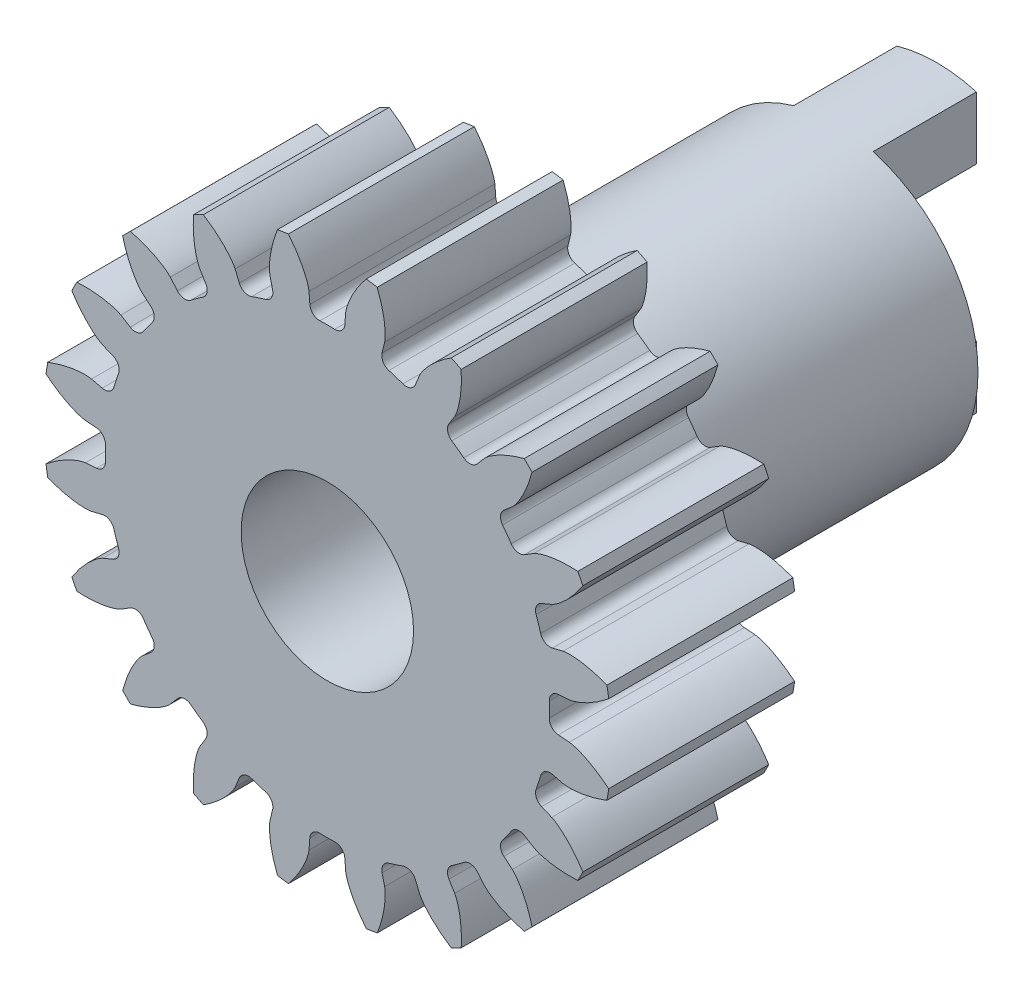
SolidWorks part; units mm, degrees
ref_plane "Front Plane" through (0, 0, 0) normal (0, 0, 1) x (1, 0, 0)
ref_plane "Top Plane" through (0, 0, 0) normal (0, 1, 0) x (1, 0, 0)
ref_plane "Right Plane" through (0, 0, 0) normal (1, 0, 0) x (0, 0, -1)
ref_axis "Gear Axis" through (0, 0, -43.7625) along (0, 0, 1)
sketch "Blank Sketch" plane through (0, 0, 0) normal (0, 0, 1) x (1, 0, 0)
  circle A0 centre (0, 0) radius 13.75
  dimension "OD" = 27.5
extrude "Blank" add sketch "Blank Sketch" along normal blind 9
sketch "Tooth Space Sketch" plane through (0, 0, 0) normal (0, 0, 1) x (1, 0, 0)
  line L0 (11.7126, 0.8876) -> (11.1829, 0.8474)
  line L1 (11.7126, -0.8876) -> (11.1829, -0.8474)
  line L2 (14.705, 2.9601) -> (14.705, -2.9601)
  arc A0 (11.1829, 0.8474) -> (10.744, 0.358) centre (11.2188, 0.3738) ccw
  arc A1 (10.744, -0.358) -> (11.1829, -0.8474) centre (11.2188, -0.3738) ccw
  arc A2 (10.744, -0.358) -> (10.744, 0.358) centre (0, 0) ccw
  spline S0 degree 4 poles (11.7126, 0.8876) (11.718, 0.8881) (11.7333, 0.8898) (11.7621, 0.8941) (11.8087, 0.9028) (11.8679, 0.9161) (11.9438, 0.936) (12.0325, 0.9629) (12.1291, 0.9959) (12.2333, 1.0356) (12.3362, 1.0785) (12.4379, 1.1244) (12.5383, 1.1729) (12.6587, 1.2348) (12.8015, 1.3135) (12.9658, 1.4118) (13.1489, 1.5308) (13.3319, 1.66) (13.5089, 1.7935) (13.6838, 1.9356) (13.8504, 2.0781) (14.0193, 2.2333) (14.173, 2.3803) (14.3404, 2.5526) (14.474, 2.694) (14.6449, 2.8885) (14.7442, 3.0057) (14.8584, 3.1456) (14.9081, 3.2092) (14.9387, 3.2482) knots 0 0 0 0 0 0.005377 0.015084 0.028532 0.04661 0.064855 0.092111 0.119476 0.146842 0.174209 0.201575 0.228941 0.256307 0.307035 0.361767 0.4165 0.471232 0.525964 0.580697 0.635429 0.690161 0.744894 0.799626 0.854358 0.909091 0.954545 1 1 1 1 1 construction
  spline S1 degree 4 poles (11.7126, 0.8876) (11.718, 0.8881) (11.7333, 0.8898) (11.7621, 0.8941) (11.8087, 0.9028) (11.8679, 0.9161) (11.9438, 0.936) (12.0325, 0.9629) (12.1291, 0.9959) (12.2333, 1.0356) (12.3362, 1.0785) (12.4379, 1.1244) (12.5383, 1.1729) (12.6587, 1.2348) (12.8015, 1.3135) (12.9658, 1.4118) (13.1489, 1.5308) (13.3319, 1.66) (13.5089, 1.7935) (13.6838, 1.9356) (13.8504, 2.0781) (14.0193, 2.2333) (14.173, 2.3803) (14.3404, 2.5526) (14.474, 2.694) (14.6078, 2.8463) (14.6723, 2.9214) (14.705, 2.9601) knots 0 0 0 0 0 0.005377 0.015084 0.028532 0.04661 0.064855 0.092111 0.119476 0.146842 0.174209 0.201575 0.228941 0.256307 0.307035 0.361767 0.4165 0.471232 0.525964 0.580697 0.635429 0.690161 0.744894 0.799626 0.854358 0.909091 0.909091 0.909091 0.909091 0.909091
  spline S2 degree 4 poles (11.7126, -0.8876) (11.718, -0.8881) (11.7333, -0.8898) (11.7621, -0.8941) (11.8087, -0.9028) (11.8679, -0.9161) (11.9438, -0.936) (12.0325, -0.9629) (12.1291, -0.9959) (12.2333, -1.0356) (12.3362, -1.0785) (12.4379, -1.1244) (12.5383, -1.1729) (12.6587, -1.2348) (12.8015, -1.3135) (12.9658, -1.4118) (13.1489, -1.5308) (13.3319, -1.66) (13.5089, -1.7935) (13.6838, -1.9356) (13.8504, -2.0781) (14.0193, -2.2333) (14.173, -2.3803) (14.3404, -2.5526) (14.474, -2.694) (14.6449, -2.8885) (14.7442, -3.0057) (14.8584, -3.1456) (14.9081, -3.2092) (14.9387, -3.2482) knots 0 0 0 0 0 0.005377 0.015084 0.028532 0.04661 0.064855 0.092111 0.119476 0.146842 0.174209 0.201575 0.228941 0.256307 0.307035 0.361767 0.4165 0.471232 0.525964 0.580697 0.635429 0.690161 0.744894 0.799626 0.854358 0.909091 0.954545 1 1 1 1 1 construction
  spline S3 degree 4 poles (11.7126, -0.8876) (11.718, -0.8881) (11.7333, -0.8898) (11.7621, -0.8941) (11.8087, -0.9028) (11.8679, -0.9161) (11.9438, -0.936) (12.0325, -0.9629) (12.1291, -0.9959) (12.2333, -1.0356) (12.3362, -1.0785) (12.4379, -1.1244) (12.5383, -1.1729) (12.6587, -1.2348) (12.8015, -1.3135) (12.9658, -1.4118) (13.1489, -1.5308) (13.3319, -1.66) (13.5089, -1.7935) (13.6838, -1.9356) (13.8504, -2.0781) (14.0193, -2.2333) (14.173, -2.3803) (14.3404, -2.5526) (14.474, -2.694) (14.6078, -2.8463) (14.6723, -2.9214) (14.705, -2.9601) knots 0 0 0 0 0 0.005377 0.015084 0.028532 0.04661 0.064855 0.092111 0.119476 0.146842 0.174209 0.201575 0.228941 0.256307 0.307035 0.361767 0.4165 0.471232 0.525964 0.580697 0.635429 0.690161 0.744894 0.799626 0.854358 0.909091 0.909091 0.909091 0.909091 0.909091
  dimension "Root" = 10.75
  dimension "Fillet" = 0.475
extrude "Tooth Space" cut sketch "Tooth Space Sketch" against normal through all both and the other way through all both
pattern_circular "Teeth" count 20 over 360 about axis through (0, 0, -43.7625) along (0, 0, 1) of "Tooth Space"
sketch "Bore Sketch" plane through (0, 0, 0) normal (0, 0, 1) x (1, 0, 0)
  circle A0 centre (0, 0) radius 4.175
  dimension "Bore" = 8.35
extrude "Bore" cut sketch "Bore Sketch" against normal through all both and the other way through all both
sketch "Sketch1" plane through (0, 0, 9) normal (0, 0, 1) x (1, 0, 0)
  circle A0 centre (0, 0) radius 4.175 construction
  circle A1 centre (0, 0) radius 4.175
  circle A4 centre (0, 0) radius 7
  dimension "D1" = 14
extrude "Boss-Extrude1" add sketch "Sketch1" against normal blind 50.25
ref_plane "Plane1" through (0, 0, -20.5) normal (0, 0, 1) x (1, 0, 0)
split "Split1" trim tools "Plane1" bodies to split 105 resulting bodies 106
sketch "Sketch2" plane through (0, 0, -20.5) normal (0, 0, -1) x (-1, 0, 0)
  line L0 (-1.925, 6.7301) -> (-1.925, -6.7301)
  line L1 (1.925, 6.7301) -> (1.925, -6.7301)
  circle A0 centre (0, 0) radius 7 construction
  arc A1 (-1.925, 6.7301) -> (-1.925, -6.7301) centre (0, 0) ccw
  arc A2 (1.925, 6.7301) -> (-1.925, 6.7301) centre (0, 0) ccw construction
  arc A3 (-1.925, -6.7301) -> (1.925, -6.7301) centre (0, 0) ccw construction
  arc A4 (1.925, -6.7301) -> (1.925, 6.7301) centre (0, 0) ccw
  dimension "D1" = 1.925
  dimension "D2" = 1.925
extrude "Cut-Extrude1" cut sketch "Sketch2" against normal blind 5
equation "\"No. of Teeth\"= 20"
equation "\"Module\"= 1.25"
equation "\"Bore Diameter\"= 8.35"
equation "\"Pressure Angle\"= 20"
equation "\"Outer Diameter\"= ( \"No. of Teeth\" + 2 ) * \"Module\""
equation "\"Pitch Diameter\"= \"No. of Teeth\" * \"Module\""
equation "\"Backlash\"= IIF ( \"Module\" <= 1 , 0.3 * \"Module\" , 0.3 )"
equation "\"Arc Length\"= ( ( \"Module\" * pi ) / 2 + \"Backlash\" )"
equation "\"Fillet Radius\"= 0.38 * \"Module\""
equation "\"Tooth Depth\"= IIF ( \"Module\" <= 1.25 , \"Module\" * 2.4 , \"Module\" * 2.25 )"
equation "\"Face Width\"= 9"
equation "\"Root Diameter\"= \"Outer Diameter\" - 2 * \"Tooth Depth\""
equation "\"Base Diameter\"= \"Pitch Diameter\" * cos ( \"Pressure Angle\" )"
equation "\"Base Radius\"= \"Base Diameter\" / 2"
equation "\"Tooth Thickness\"= \"Module\" * pi - \"Arc Length\""
equation "\"Half Space Angle\"= ( \"Arc Length\" / \"Pitch Diameter\" ) * 180 / pi"
equation "\"Involute Fn\"= tan ( \"Pressure Angle\" ) - \"Pressure Angle\" * pi / 180"
equation "\"Flank Offset\"= \"Arc Length\" / \"Pitch Diameter\" - \"Involute Fn\""
equation "\"Tip Cap Diameter\"= \"Outer Diameter\" + 2 * \"Module\""
equation "\"Flank Start Diameter\"= IIF ( \"Base Diameter\" >= ( \"Root Diameter\" + 3 * \"Fillet Radius\" ) , \"Base Diameter\" , \"Root Diameter\" + 3 * \"Fillet Radius\" )"
equation "\"Involute t1\"= ( abs ( ( \"Flank Start Diameter\" / \"Base Diameter\" ) ^ 2 - 1 ) ) ^ 0.5"
equation "\"Involute t2\"= ( abs ( ( \"Tip Cap Diameter\" / \"Base Diameter\" ) ^ 2 - 1 ) ) ^ 0.5"
equation "\"Flank Arc Radius\"= ( \"Pitch Diameter\" / 2 ) * sin ( \"Pressure Angle\" )"
equation "\"Flank Centre Angle\"= \"Half Space Angle\" + \"Pressure Angle\""
equation "\"OD@Blank Sketch\"= \"Outer Diameter\""
equation "\"Width@Blank\"= \"Face Width\""
equation "\"Root@Tooth Space Sketch\"= \"Root Diameter\" / 2"
equation "\"Fillet@Tooth Space Sketch\"= \"Fillet Radius\""
equation "\"Count@Teeth\"= \"No. of Teeth\""
equation "\"Bore@Bore Sketch\"= \"Bore Diameter\""
